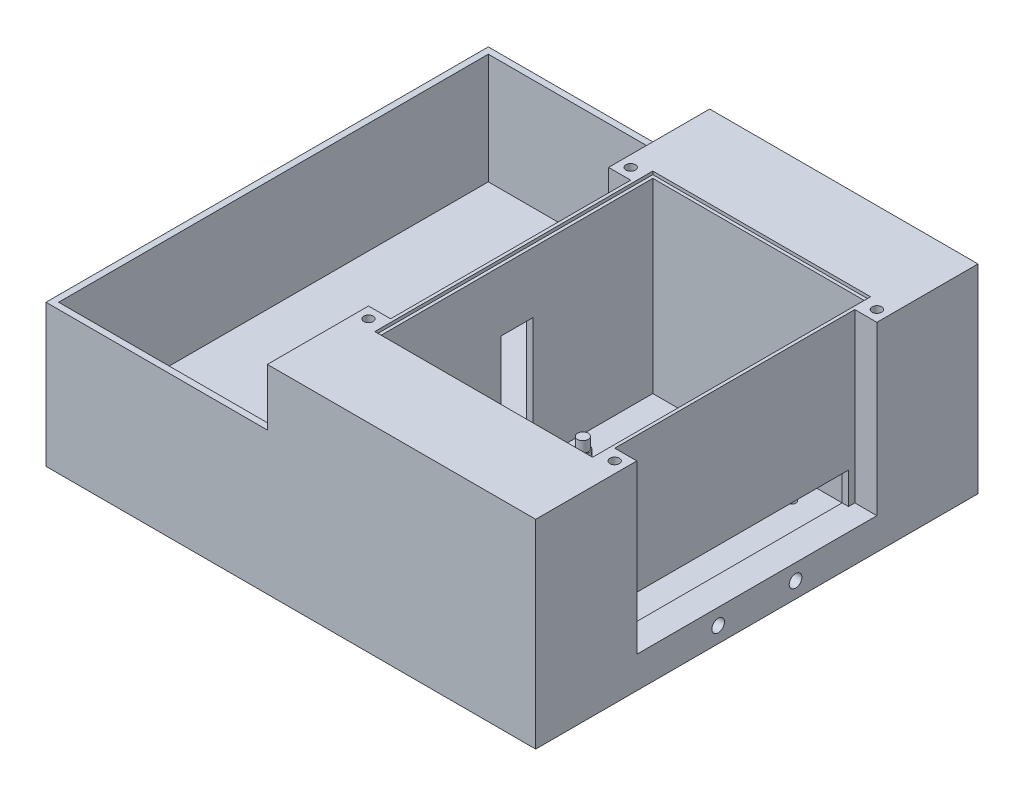
SolidWorks part; units mm, degrees
ref_plane "Спереди" through (0, 0, 0) normal (0, 0, 1) x (1, 0, 0)
ref_plane "Сверху" through (0, 0, 0) normal (0, 1, 0) x (1, 0, 0)
ref_plane "Справа" through (0, 0, 0) normal (1, 0, 0) x (0, 0, -1)
sketch "Эскиз1" plane through (0, 0, 0) normal (0, 1, 0) x (1, 0, 0)
  line L1 (-78.6567, 28.1694) -> (76.3433, 28.1694)
  line L2 (-78.6567, 28.1694) -> (-78.6567, -61.8306)
  line L3 (-78.6567, -61.8306) -> (76.3433, -61.8306)
  line L4 (76.3433, 28.1694) -> (76.3433, -61.8306)
  dimension "D1" = 155
  dimension "D2" = 90
extrude "Бобышка-Вытянуть2" add sketch "Эскиз1" along normal blind 10
sketch "Эскиз2" plane through (0, 10, 0) normal (0, 1, 0) x (1, 0, 0)
  line L0 (76.3433, 28.1694) -> (61.3433, 28.1694)
  line L1 (76.3433, 28.1694) -> (-78.6567, 28.1694) construction
  line L2 (61.3433, 28.1694) -> (61.3433, -61.8306)
  line L3 (-78.6567, -61.8306) -> (76.3433, -61.8306) construction
  line L4 (61.3433, -61.8306) -> (-9.5863, -61.8306)
  line L5 (-9.5863, -61.8306) -> (-9.5863, 28.1694)
  line L6 (-9.5863, 28.1694) -> (61.3433, 28.1694)
  line L7 (59.3433, 26.1694) -> (59.3433, -59.8306)
  line L8 (59.3433, -59.8306) -> (-7.5863, -59.8306)
  line L9 (-7.5863, -59.8306) -> (-7.5863, 26.1694)
  line L10 (-7.5863, 26.1694) -> (59.3433, 26.1694)
  line L11 (57.3433, 28.1694) -> (57.3433, 26.1694)
  line L12 (57.3433, 28.1694) -> (49.3433, 28.1694)
  line L13 (49.3433, 28.1694) -> (49.3433, 26.1694)
  line L14 (49.3433, 26.1694) -> (57.3433, 26.1694)
  line L15 (49.3433, -59.8306) -> (49.3433, -61.8306)
  line L16 (49.3433, -61.8306) -> (57.3433, -61.8306)
  line L17 (57.3433, -61.8306) -> (57.3433, -59.8306)
  line L18 (57.3433, -59.8306) -> (49.3433, -59.8306)
  dimension "D1" = 15
  dimension "D2" = 70.9296
  dimension "D4" = 2
  dimension "D5" = 8
  dimension "D3" = 2
extrude "Вырез-Вытянуть1" cut sketch "Эскиз2" against normal blind 7 contours L6 L13 L10 L11 | L10 L9 L8 L7 | L4 L17 L8 L15 region at (53.3433, 10, -27.1694) region at (53.3433, 10, 60.8306) region at (25.8785, 10, 16.8306)
sketch "Эскиз3" plane through (0, 3, 0) normal (0, 1, 0) x (1, 0, 0)
  line L0 (58.2878, 25.2665) -> (38.2878, 25.2665)
  circle A0 centre (-1.5406, -2.0216) radius 2
  circle A1 centre (-1.5406, -22.0216) radius 2
  circle A2 centre (26.4594, -2.0216) radius 2
  circle A3 centre (26.4594, -22.0216) radius 2
  dimension "D12" = 4
  dimension "D13" = 4
  dimension "D14" = 4
  dimension "D15" = 4
  dimension "D1" = 20
extrude "Бобышка-Вытянуть3" add sketch "Эскиз3" along normal blind 2 contours A0 | A1 | A2 | A3 region at (-1.5406, 3, 2.0216) region at (-1.5406, 3, 22.0216) region at (26.4594, 3, 2.0216) region at (26.4594, 3, 22.0216)
sketch "Эскиз4" plane through (0, 5, 0) normal (0, 1, 0) x (1, 0, 0)
  circle A0 centre (-1.5406, -2.0216) radius 1.7
  circle A1 centre (-1.5406, -22.0216) radius 1.7
  circle A2 centre (26.4594, -22.0216) radius 1.7
  circle A3 centre (26.4594, -2.0216) radius 1.7
  dimension "D1" = 3.4
  dimension "D2" = 3.4
  dimension "D3" = 3.4
  dimension "D4" = 3.4
extrude "Бобышка-Вытянуть4" add sketch "Эскиз4" along normal blind 3.4 contours A2 | A3 | A1 | A0
sketch "Эскиз5" plane through (0, 10, 0) normal (0, 1, 0) x (1, 0, 0)
  line L0 (-9.5863, 28.1694) -> (61.3433, 28.1694)
  line L1 (-9.5863, 26.1694) -> (-9.5863, -61.8306)
  line L2 (-78.6567, -61.8306) -> (49.3433, -61.8306) construction
  line L3 (-9.5863, 26.1694) -> (-9.5863, 28.1694)
  line L4 (49.3433, 28.1694) -> (-78.6567, 28.1694) construction
  line L5 (-9.5863, 28.1694) -> (-9.5863, -61.8306)
  line L6 (61.3433, 26.1694) -> (61.3433, 28.1694)
  line L7 (76.3433, 28.1694) -> (57.3433, 28.1694) construction
  line L8 (61.3433, 28.1694) -> (61.3433, 26.1694)
  line L9 (61.3433, 26.1694) -> (61.3433, -61.8306)
  line L10 (57.3433, -61.8306) -> (76.3433, -61.8306) construction
  line L11 (61.3433, -61.8306) -> (-9.5863, -61.8306)
  line L12 (49.3433, -59.8306) -> (57.3433, -59.8306)
  line L13 (57.3433, -59.8306) -> (59.3433, -59.8306)
  line L14 (59.3433, -59.8306) -> (59.3433, 26.1694)
  line L15 (-7.5863, 26.1694) -> (59.3433, 26.1694)
  line L16 (-7.5863, 26.1694) -> (-7.5863, -59.8306)
  line L17 (-7.5863, -59.8306) -> (49.3433, -59.8306)
  line L18 (-9.5863, -61.8306) -> (61.3433, -61.8306)
  line L19 (61.3433, -61.8306) -> (61.3433, 28.1694)
  line L20 (61.3433, 28.1694) -> (-9.5863, 28.1694)
  line L21 (-7.5863, 26.1694) -> (59.3433, 26.1694)
  line L22 (59.3433, 26.1694) -> (59.3433, -59.8306)
  line L23 (59.3433, -59.8306) -> (-7.5863, -59.8306)
  line L24 (-7.5863, -59.8306) -> (-7.5863, 26.1694)
  dimension "D1" = 2
  dimension "D2" = 2
extrude "Бобышка-Вытянуть5" add sketch "Эскиз5" along normal blind 14 contours L11 L1 L3 L0 L6 L9 | L16 L15 L14 L13 L12 L17
sketch "Эскиз6" plane through (0, 10, 0) normal (0, 1, 0) x (1, 0, 0)
  line L1 (61.3433, 28.1694) -> (68.3433, 28.1694)
  line L2 (61.3433, 28.1694) -> (61.3433, 21.1694)
  line L3 (61.3433, 21.1694) -> (68.3433, 21.1694)
  line L4 (68.3433, 28.1694) -> (68.3433, 21.1694)
  line L5 (61.3433, -61.8306) -> (68.3433, -61.8306)
  line L6 (61.3433, -61.8306) -> (61.3433, -54.8306)
  line L7 (61.3433, -54.8306) -> (68.3433, -54.8306)
  line L8 (68.3433, -61.8306) -> (68.3433, -54.8306)
  line L9 (-9.5863, -61.8306) -> (-16.5863, -61.8306)
  line L10 (-9.5863, -61.8306) -> (-9.5863, -54.8306)
  line L11 (-9.5863, -54.8306) -> (-16.5863, -54.8306)
  line L12 (-16.5863, -61.8306) -> (-16.5863, -54.8306)
  line L13 (-9.5863, 28.1694) -> (-16.5863, 28.1694)
  line L14 (-9.5863, 28.1694) -> (-9.5863, 21.1694)
  line L15 (-9.5863, 21.1694) -> (-16.5863, 21.1694)
  line L16 (-16.5863, 28.1694) -> (-16.5863, 21.1694)
  dimension "D1" = 7
  dimension "D2" = 7
  dimension "D3" = 7
  dimension "D4" = 7
  dimension "D5" = 7
  dimension "D6" = 7
  dimension "D7" = 7
  dimension "D8" = 7
extrude "Бобышка-Вытянуть6" add sketch "Эскиз6" along normal blind 14
sketch "Эскиз16" plane through (0, 24, 0) normal (0, 1, 0) x (1, 0, 0)
  line L20 (-8.5863, -60.8306) -> (60.3433, -60.8306)
  line L21 (60.3433, -60.8306) -> (60.3433, 27.1694)
  line L22 (-8.5863, 27.1694) -> (-8.5863, -60.8306)
  line L23 (60.3433, 27.1694) -> (-8.5863, 27.1694)
  line L24 (-8.5863, -60.8306) -> (60.3433, -60.8306)
  line L25 (60.3433, -60.8306) -> (60.3433, 27.1694)
  line L26 (-8.5863, 27.1694) -> (-8.5863, -60.8306)
  line L27 (60.3433, 27.1694) -> (-8.5863, 27.1694)
  dimension "D1" = 1
extrude "Вырез-Вытянуть3" cut sketch "Эскиз16" against normal blind 1
sketch "Эскиз17" plane through (0, 24, 0) normal (0, 1, 0) x (1, 0, 0)
  line L0 (-16.5863, 28.1694) -> (-9.5863, 21.1694)
  line L1 (-9.5863, -54.8306) -> (-16.5863, -61.8306)
  line L2 (61.3433, -54.8306) -> (68.3433, -61.8306)
  line L3 (68.3433, 28.1694) -> (61.3433, 21.1694)
  circle A0 centre (-13.0863, 24.6694) radius 1.5
  circle A1 centre (64.8433, 24.6694) radius 1.5
  circle A2 centre (-13.0863, -58.3306) radius 1.5
  circle A3 centre (64.8433, -58.3306) radius 1.5
  dimension "D1" = 3
  dimension "D2" = 3
  dimension "D3" = 3
  dimension "D4" = 3
extrude "Вырез-Вытянуть4" cut sketch "Эскиз17" against normal blind 5 contours A1 | A3 | A2 | A0
sketch "Эскиз18" plane through (76.3433, 0, 0) normal (1, 0, 0) x (0, 0, -1)
  line L0 (-61.8306, 0) -> (-41.3306, 0)
  line L1 (-61.8306, 0) -> (28.1694, 0) construction
  line L2 (28.1694, 0) -> (7.6694, 0)
  line L3 (-61.8306, 10) -> (28.1694, 10) construction
  line L4 (-41.3306, 0) -> (7.6694, 0)
  line L5 (-41.3306, 0) -> (-41.3306, 10)
  line L6 (-41.3306, 10) -> (7.6694, 10)
  line L7 (7.6694, 0) -> (7.6694, 10)
  line L8 (-16.8306, 10) -> (-16.8306, 0)
  line L9 (-16.8306, 0) -> (-41.3306, 10)
  line L10 (-41.3306, 0) -> (-16.8306, 10)
  line L11 (-16.8306, 10) -> (7.6694, 0)
  line L12 (7.6694, 10) -> (-16.8306, 0)
  circle A0 centre (-29.0806, 5) radius 2
  circle A1 centre (-4.5806, 5) radius 2
  dimension "D3" = 4
  dimension "D4" = 4
  dimension "D1" = 20.5
  dimension "D2" = 20.5
extrude "Вырез-Вытянуть5" cut sketch "Эскиз18" against normal blind 18 contours A0 | A1
sketch "Эскиз20" plane through (-78.6567, 0, 0) normal (-1, 0, 0) x (0, 0, 1)
  line L0 (-28.1694, 0) -> (-7.6694, 0)
  line L1 (-28.1694, 0) -> (61.8306, 0) construction
  line L2 (61.8306, 0) -> (41.3306, 0)
  line L3 (54.8306, 10) -> (-21.1694, 10) construction
  line L4 (-7.6694, 0) -> (41.3306, 0)
  line L5 (-7.6694, 0) -> (-7.6694, 10)
  line L6 (-7.6694, 10) -> (41.3306, 10)
  line L7 (41.3306, 0) -> (41.3306, 10)
  line L8 (16.8306, 10) -> (16.8306, 0)
  line L9 (16.8306, 0) -> (41.3306, 10)
  line L10 (41.3306, 0) -> (16.8306, 10)
  line L11 (16.8306, 10) -> (-7.6694, 0)
  line L12 (-7.6694, 10) -> (16.8306, 0)
  circle A0 centre (4.5806, 5) radius 2
  circle A1 centre (29.0806, 5) radius 2
  dimension "D3" = 4
  dimension "D4" = 4
  dimension "D1" = 20.5
  dimension "D2" = 20.5
extrude "Вырез-Вытянуть8" cut sketch "Эскиз20" against normal blind 17 contours A0 | A1
sketch "Эскиз21" plane through (0, 0, 61.8306) normal (0, 0, 1) x (1, 0, 0)
  line L0 (76.3433, 0) -> (-1.6567, 0)
  line L1 (-78.6567, 0) -> (76.3433, 0) construction
  line L3 (76.3433, 0) -> (69.3433, 0)
  line L4 (76.3433, 0) -> (76.3433, -7)
  line L5 (76.3433, -7) -> (69.3433, -7)
  line L6 (69.3433, 0) -> (69.3433, -7)
  line L7 (-1.6567, 0) -> (5.3433, 0)
  line L8 (-1.6567, 0) -> (-1.6567, -7)
  line L9 (-1.6567, -7) -> (5.3433, -7)
  line L10 (5.3433, 0) -> (5.3433, -7)
  circle A0 centre (1.8433, -3.5) radius 1
  circle A1 centre (72.8433, -3.5) radius 1
  dimension "D6" = 2
  dimension "D7" = 2
  dimension "D1" = 78
  dimension "D2" = 7
  dimension "D3" = 7
  dimension "D4" = 7
  dimension "D5" = 7
extrude "Бобышка-Вытянуть7" add sketch "Эскиз21" against normal blind 90 contours L10 L8 L9 A0 | L3 L6 L5 L4 region at (5.2443, -3.5, 61.8306)
sketch "Эскиз22" plane through (0, -7, 0) normal (0, -1, 0) x (1, 0, 0)
  line L0 (76.3433, 61.8306) -> (76.3433, 56.8306)
  line L1 (76.3433, -28.1694) -> (76.3433, 61.8306) construction
  line L2 (76.3433, -28.1694) -> (76.3433, -23.1694)
  line L4 (76.3433, -23.1694) -> (-9.8938, -23.1694)
  line L5 (76.3433, -23.1694) -> (76.3433, 56.8306)
  line L6 (76.3433, 56.8306) -> (-9.8938, 56.8306)
  line L7 (-9.8938, -23.1694) -> (-9.8938, 56.8306)
  dimension "D1" = 5
  dimension "D2" = 5
extrude "Вырез-Вытянуть11" cut sketch "Эскиз22" against normal blind 7 contours L6 L7 L4 L5
sketch "Эскиз23" plane through (0, 0, 61.8306) normal (0, 0, 1) x (1, 0, 0)
  line L0 (69.3433, 0) -> (76.3433, -7)
  circle A0 centre (72.8433, -3.5) radius 1
  dimension "D1" = 2
extrude "Вырез-Вытянуть12" cut sketch "Эскиз23" against normal blind 90 contours A0
sketch "Эскиз25" plane through (49.3433, 0, 0) normal (1, 0, 0) x (0, 0, -1)
  line L0 (-59.8306, 3) -> (-61.8306, 3) construction
  line L1 (-61.8306, 10) -> (-59.8306, 10)
  line L2 (-61.8306, 10) -> (-61.8306, 3)
  line L3 (-61.8306, 3) -> (-59.8306, 3)
  line L4 (-59.8306, 10) -> (-59.8306, 3)
  line L6 (26.1694, 3) -> (28.1694, 3)
  line L7 (26.1694, 3) -> (26.1694, 10)
  line L8 (26.1694, 10) -> (28.1694, 10)
  line L9 (28.1694, 3) -> (28.1694, 10)
extrude "Бобышка-Вытянуть8" add sketch "Эскиз25" along normal blind 10
sketch "Эскиз26" plane through (61.3433, 0, 0) normal (1, 0, 0) x (0, 0, -1)
  line L0 (-54.8306, 10) -> (-52.8306, 10)
  line L1 (-54.8306, 10) -> (21.1694, 10) construction
  line L2 (21.1694, 10) -> (19.1694, 10)
  line L4 (-52.8306, 10) -> (19.1694, 10)
  line L5 (-52.8306, 10) -> (-52.8306, 20)
  line L6 (-52.8306, 20) -> (19.1694, 20)
  line L7 (19.1694, 10) -> (19.1694, 20)
  line M5 (-54.8306, 10) -> (21.1694, 10)
  dimension "D1" = 2
  dimension "D2" = 2
  dimension "D3" = 10
extrude "Вырез-Вытянуть13" cut sketch "Эскиз26" against normal blind 16 contours L7 L6 L5 M5 region at (61.3433, 15, 16.8306)
sketch "Эскиз27" plane through (0, 0, 61.8306) normal (0, 0, 1) x (1, 0, 0)
  line L0 (76.3433, 10) -> (76.3433, -7) construction
  line L1 (-1.6567, 0) -> (5.3433, 0)
  line L2 (-1.6567, 0) -> (-1.6567, 10)
  line L3 (-1.6567, 10) -> (5.3433, 10)
  line L4 (5.3433, 0) -> (5.3433, 10)
  line L5 (69.3433, 0) -> (76.3433, 0)
  line L6 (69.3433, 0) -> (69.3433, 10)
  line L7 (69.3433, 10) -> (76.3433, 10)
  line L8 (76.3433, 0) -> (76.3433, 10)
  line L9 (-1.6567, 10) -> (5.3433, 0)
  line L10 (69.3433, 10) -> (76.3433, 0)
  circle A0 centre (1.8433, 5) radius 1
  circle A1 centre (72.8433, 5) radius 1
  dimension "D2" = 2
  dimension "D3" = 2
  dimension "D1" = 10
extrude "Вырез-Вытянуть14" cut sketch "Эскиз27" against normal blind 7 contours A1 | A0
sketch "Эскиз28" plane through (0, 0, -28.1694) normal (0, 0, -1) x (-1, 0, 0)
  line L0 (-76.3433, 10) -> (-69.3433, 0)
  line L1 (-69.3433, 0) -> (-76.3433, 0)
  line L2 (-69.3433, 0) -> (-69.3433, 10)
  line L3 (-69.3433, 10) -> (-76.3433, 10)
  line L4 (-76.3433, 0) -> (-76.3433, 10)
  line L5 (-5.3433, 0) -> (1.6567, 0)
  line L6 (-5.3433, 0) -> (-5.3433, 10)
  line L7 (-5.3433, 10) -> (1.6567, 10)
  line L8 (1.6567, 0) -> (1.6567, 10)
  line L9 (-5.3433, 10) -> (1.6567, 0)
  circle A0 centre (-72.8433, 5) radius 1
  circle A1 centre (-1.8433, 5) radius 1
  dimension "D2" = 2
  dimension "D3" = 2
  dimension "D1" = 7
extrude "Вырез-Вытянуть15" cut sketch "Эскиз28" against normal blind 7 contours A1 | A0
sketch "Эскиз30" plane through (0, -7, 0) normal (0, -1, 0) x (1, 0, 0)
  line L0 (5.3433, -28.1694) -> (5.3433, -23.1694) construction
  line L1 (-1.6567, 61.8306) -> (5.3433, 61.8306)
  line L2 (-1.6567, 61.8306) -> (-1.6567, 56.8306)
  line L3 (-1.6567, 56.8306) -> (5.3433, 56.8306)
  line L4 (5.3433, 61.8306) -> (5.3433, 56.8306)
  line L5 (69.3433, 61.8306) -> (76.3433, 61.8306)
  line L6 (69.3433, 61.8306) -> (69.3433, 56.8306)
  line L7 (69.3433, 56.8306) -> (76.3433, 56.8306)
  line L8 (76.3433, 61.8306) -> (76.3433, 56.8306)
  line L9 (-1.6567, -23.1694) -> (5.3433, -23.1694)
  line L10 (-1.6567, -23.1694) -> (-1.6567, -28.1694)
  line L11 (-1.6567, -28.1694) -> (5.3433, -28.1694)
  line L12 (5.3433, -23.1694) -> (5.3433, -28.1694)
  line L13 (69.3433, -28.1694) -> (5.3433, -28.1694) construction
  line L15 (69.3433, -23.1694) -> (76.3433, -23.1694)
  line L16 (69.3433, -23.1694) -> (69.3433, -28.1694)
  line L17 (69.3433, -28.1694) -> (76.3433, -28.1694)
  line L18 (76.3433, -23.1694) -> (76.3433, -28.1694)
extrude "Вырез-Вытянуть16" cut sketch "Эскиз30" against normal blind 7
sketch "Эскиз32" plane through (76.3433, 0, 0) normal (1, 0, 0) x (0, 0, -1)
  line L1 (-61.8306, 10) -> (28.1694, 10)
  line L2 (-61.8306, 10) -> (-61.8306, 0)
  line L3 (-61.8306, 0) -> (28.1694, 0)
  line L4 (28.1694, 10) -> (28.1694, 0)
extrude "Вырез-Вытянуть17" cut sketch "Эскиз32" against normal blind 8
sketch "Эскиз36" plane through (-78.6567, 0, 0) normal (-1, 0, 0) x (0, 0, 1)
  line L0 (61.8306, 10) -> (61.8306, 0) construction
  line L1 (-28.1694, 10) -> (61.8306, 10)
  line L2 (-28.1694, 10) -> (-28.1694, 0)
  line L3 (-28.1694, 0) -> (61.8306, 0)
  line L4 (61.8306, 10) -> (61.8306, 0)
  line L5 (-28.1694, 0) -> (61.8306, 0) construction
  circle A0 centre (4.5806, 5) radius 2
  circle A1 centre (29.0806, 5) radius 2
extrude "Бобышка-Вытянуть9" add sketch "Эскиз36" along normal blind 8
sketch "Эскиз37" plane through (0, 0, 61.8306) normal (0, 0, 1) x (1, 0, 0)
  circle A0 centre (1.8433, 5) radius 1
extrude "Бобышка-Вытянуть10" add sketch "Эскиз37" against normal blind 2
sketch "Эскиз39" plane through (0, 0, -28.1694) normal (0, 0, -1) x (-1, 0, 0)
  circle A0 centre (-1.8433, 5) radius 1
extrude "Бобышка-Вытянуть11" add sketch "Эскиз39" against normal blind 2
sketch "Эскиз42" plane through (0, 0, -28.1694) normal (0, 0, -1) x (-1, 0, 0)
  line L0 (-68.3433, 24) -> (-68.3433, 0)
  line L1 (-68.3433, 0) -> (86.6567, 0)
  line L2 (86.6567, 0) -> (86.6567, 10)
  line L3 (86.6567, 10) -> (16.5863, 10)
  line L4 (16.5863, 10) -> (16.5863, 24)
  line L5 (16.5863, 24) -> (-68.3433, 24)
extrude "Бобышка-Вытянуть12" add sketch "Эскиз42" along normal blind 25
sketch "Эскиз43" plane through (0, 0, 61.8306) normal (0, 0, 1) x (1, 0, 0)
  line L0 (-86.6567, 10) -> (-86.6567, 0)
  line L1 (-86.6567, 0) -> (68.3433, 0)
  line L2 (68.3433, 0) -> (68.3433, 24)
  line L3 (68.3433, 24) -> (-16.5863, 24)
  line L4 (-16.5863, 24) -> (-16.5863, 10)
  line L5 (-16.5863, 24) -> (-16.5863, 10) construction
  line L6 (-86.6567, 10) -> (-16.5863, 10) construction
  line L7 (-16.5863, 10) -> (-86.6567, 10)
extrude "Бобышка-Вытянуть13" add sketch "Эскиз43" along normal blind 25
sketch "Эскиз46" plane through (0, 10, 0) normal (0, 1, 0) x (1, 0, 0)
  line L6 (-16.5863, 51.1694) -> (-16.5863, 53.1694)
  line L7 (-16.5863, 53.1694) -> (-86.6567, 53.1694)
  line L8 (-86.6567, 53.1694) -> (-86.6567, -86.8306)
  line L9 (-16.5863, -84.8306) -> (-84.6567, -84.8306)
  line L10 (-84.6567, -84.8306) -> (-84.6567, 51.1694)
  line L11 (-84.6567, 51.1694) -> (-16.5863, 51.1694)
  line L12 (-16.5863, -84.8306) -> (-84.6567, -84.8306)
  line L13 (-84.6567, -84.8306) -> (-84.6567, 51.1694)
  line L14 (-84.6567, 51.1694) -> (-16.5863, 51.1694)
  line L15 (-86.6567, -86.8306) -> (-16.5863, -86.8306)
  line L16 (-16.5863, -86.8306) -> (-16.5863, -84.8306)
  dimension "D1" = 2
extrude "Бобышка-Вытянуть14" add sketch "Эскиз46" along normal blind 35 contours L13 L14 L6 L7 L8 L15 L16 L12
sketch "Эскиз47" plane through (-9.5863, 0, 0) normal (-1, 0, 0) x (0, 0, 1)
  line L0 (16.8306, 10) -> (16.8306, 24)
  line L1 (54.8306, 10) -> (-21.1694, 10) construction
  line L2 (-21.1694, 24) -> (54.8306, 24) construction
  line L3 (16.8306, 17) -> (11.8306, 17)
  line L4 (11.8306, 17) -> (16.8306, 17)
  line L5 (16.8306, 17) -> (21.8306, 17)
  line L6 (11.8306, 17) -> (11.8306, 10)
  line L7 (21.8306, 17) -> (21.8306, 10)
  line L9 (11.8306, 17) -> (21.8306, 17)
  line L10 (11.8306, 17) -> (11.8306, 20.7964)
  line L11 (11.8306, 20.7964) -> (21.8306, 20.7964)
  line L12 (21.8306, 17) -> (21.8306, 20.7964)
  line M5 (-21.1694, 10) -> (54.8306, 10)
  dimension "D1" = 5
  dimension "D2" = 5
extrude "Вырез-Вытянуть18" cut sketch "Эскиз47" against normal blind 4 contours L3 L6 L0 M5 | L11 L10 L3 L0 | L5 L12 L11 L0 | L7 L5 L0 M5 region at (-9.5863, 13.5, 14.3306) region at (-9.5863, 13.5, 19.3306) region at (-9.5863, 18.8982, 14.3306) region at (-9.5863, 18.8982, 19.3306)
sketch "Эскиз51" plane through (0, 24, 0) normal (0, 1, 0) x (1, 0, 0)
  line L0 (-16.5863, 53.1694) -> (-16.5863, 21.1694)
  line L1 (-16.5863, 21.1694) -> (-9.5863, 21.1694)
  line L2 (-9.5863, 21.1694) -> (-9.5863, -54.8306)
  line L3 (-9.5863, -54.8306) -> (-16.5863, -54.8306)
  line L4 (-16.5863, -54.8306) -> (-16.5863, -86.8306)
  line L5 (-16.5863, -86.8306) -> (68.3433, -86.8306)
  line L6 (68.3433, -86.8306) -> (68.3433, -54.8306)
  line L7 (68.3433, -54.8306) -> (61.3433, -54.8306)
  line L8 (61.3433, -54.8306) -> (61.3433, 21.1694)
  line L9 (61.3433, 21.1694) -> (68.3433, 21.1694)
  line L10 (68.3433, 21.1694) -> (68.3433, 53.1694)
  line L11 (68.3433, 53.1694) -> (-16.5863, 53.1694)
  line L13 (-8.5863, 27.1694) -> (60.3433, 27.1694)
  line L14 (-8.5863, 27.1694) -> (-8.5863, -60.8306)
  line L15 (-8.5863, -60.8306) -> (60.3433, -60.8306)
  line L16 (60.3433, 27.1694) -> (60.3433, -60.8306)
  circle A0 centre (-13.0863, -58.3306) radius 1.5
  circle A1 centre (64.8433, -58.3306) radius 1.5
  circle A2 centre (64.8433, 24.6694) radius 1.5
  circle A3 centre (-13.0863, 24.6694) radius 1.5
extrude "Бобышка-Вытянуть15" add sketch "Эскиз51" along normal blind 39
sketch "Эскиз52" plane through (0, 23, 0) normal (0, 1, 0) x (1, 0, 0)
  line L1 (-8.5863, 27.1694) -> (60.3433, 27.1694)
  line L2 (-8.5863, 27.1694) -> (-8.5863, -60.8306)
  line L3 (-8.5863, -60.8306) -> (60.3433, -60.8306)
  line L4 (60.3433, 27.1694) -> (60.3433, -60.8306)
  line L5 (-7.5863, 26.1694) -> (59.3433, 26.1694)
  line L6 (-7.5863, 26.1694) -> (-7.5863, -59.8306)
  line L7 (-7.5863, -59.8306) -> (59.3433, -59.8306)
  line L8 (59.3433, 26.1694) -> (59.3433, -59.8306)
extrude "Бобышка-Вытянуть16" add sketch "Эскиз52" along normal blind 39
sketch "Эскиз56" plane through (-9.5863, 0, 0) normal (-1, 0, 0) x (0, 0, 1)
  line L9 (11.8306, 20.7964) -> (21.8306, 20.7964)
  line L10 (11.8306, 20.7964) -> (11.8306, 42.7964)
  line L11 (11.8306, 42.7964) -> (21.8306, 42.7964)
  line L12 (21.8306, 20.7964) -> (21.8306, 42.7964)
  dimension "D1" = 10
  dimension "D2" = 22
extrude "Вырез-Вытянуть19" cut sketch "Эскиз56" against normal blind 39
sketch "Эскиз57" plane through (0, 3, 0) normal (0, 1, 0) x (1, 0, 0)
  line L0 (59.3433, -16.8306) -> (57.2867, -16.8306)
  line L1 (59.3433, -59.8306) -> (59.3433, 26.1694) construction
  line L2 (57.2867, -16.8306) -> (57.2867, -54.8306)
  line L3 (57.2867, -54.8306) -> (41.2867, -54.8306)
  line L4 (41.2867, -54.8306) -> (41.2867, 21.1694)
  line L5 (41.2867, 21.1694) -> (57.2867, 21.1694)
  line L6 (57.2867, 21.1694) -> (57.2867, -16.8306)
  line L7 (42.2867, 18.7694) -> (41.2867, 18.7694)
  line L8 (43.6867, 20.1694) -> (43.6867, 21.1694)
  line L9 (54.8867, 20.1694) -> (54.8867, 21.1694)
  line L10 (56.2867, 18.7694) -> (57.2867, 18.7694)
  line L11 (42.2867, -52.4306) -> (41.2867, -52.4306)
  line L12 (43.6867, -53.8306) -> (43.6867, -54.8306)
  line L13 (54.8867, -53.8306) -> (54.8867, -54.8306)
  line L14 (56.2867, -52.4306) -> (57.2867, -52.4306)
  circle A0 centre (43.6867, 18.7694) radius 1.4
  circle A1 centre (54.8867, 18.7694) radius 1.4
  circle A2 centre (43.6867, -52.4306) radius 1.4
  circle A3 centre (54.8867, -52.4306) radius 1.4
  dimension "D7" = 2.8
  dimension "D11" = 2.8
  dimension "D14" = 2.8
  dimension "D17" = 2.8
  dimension "D1" = 2.0566
  dimension "D2" = 16
  dimension "D3" = 76
  dimension "D4" = 38
  dimension "D5" = 38
  dimension "D6" = 1
  dimension "D8" = 1
  dimension "D9" = 1
  dimension "D10" = 1
  dimension "D12" = 1
  dimension "D13" = 1
  dimension "D15" = 1
  dimension "D16" = 1
extrude "Вырез-Вытянуть21" cut sketch "Эскиз57" against normal blind 39 contours A3 | A2 | A1 | A0
sketch "Эскиз58" plane through (0, 45, 0) normal (0, 1, 0) x (1, 0, 0)
  line L0 (-16.5863, 21.1694) -> (-9.5863, 14.1694)
  line L1 (-9.5863, -11.8306) -> (-9.5863, 21.1694) construction
  line L2 (-16.5863, -54.8306) -> (-9.5863, -47.8306)
  line L3 (-9.5863, 21.1694) -> (-9.5863, -54.8306) construction
  line L4 (-13.0863, -51.3306) -> (-9.5863, -54.8306)
  line L5 (-13.0863, 17.6694) -> (-9.5863, 21.1694)
  line L6 (-16.5863, 21.1694) -> (-9.5863, 21.1694)
  line L7 (-9.5863, 21.1694) -> (-9.5863, 14.1694)
  line L8 (-9.5863, -47.8306) -> (-9.5863, -54.8306)
  line L9 (-9.5863, -54.8306) -> (-16.5863, -54.8306)
  circle A0 centre (-11.3363, 19.4194) radius 1.4
  circle A1 centre (-11.3363, -53.0806) radius 1.4
  dimension "D1" = 2.8
  dimension "D2" = 2.8
extrude "Бобышка-Вытянуть17" add sketch "Эскиз58" against normal blind 5 contours A1 L4 L2 L9 | A1 L4 L8 L2 | A0 L5 L6 L0 | A0 L5 L0 L7 region at (-13.5327, 45, -20.0576) region at (-10.6982, 45, -17.223) region at (-13.5327, 45, 53.7187) region at (-10.6982, 45, 50.8841)
sketch "Эскиз59" plane through (0, 45, 0) normal (0, 1, 0) x (1, 0, 0)
  line L1 (-16.5863, 21.1694) -> (-9.5863, 21.1694)
  line L2 (-16.5863, 21.1694) -> (-16.5863, -54.8306)
  line L3 (-16.5863, -54.8306) -> (-9.5863, -54.8306)
  line L4 (-9.5863, 21.1694) -> (-9.5863, -54.8306)
extrude "Вырез-Вытянуть22" cut sketch "Эскиз59" against normal blind 2
